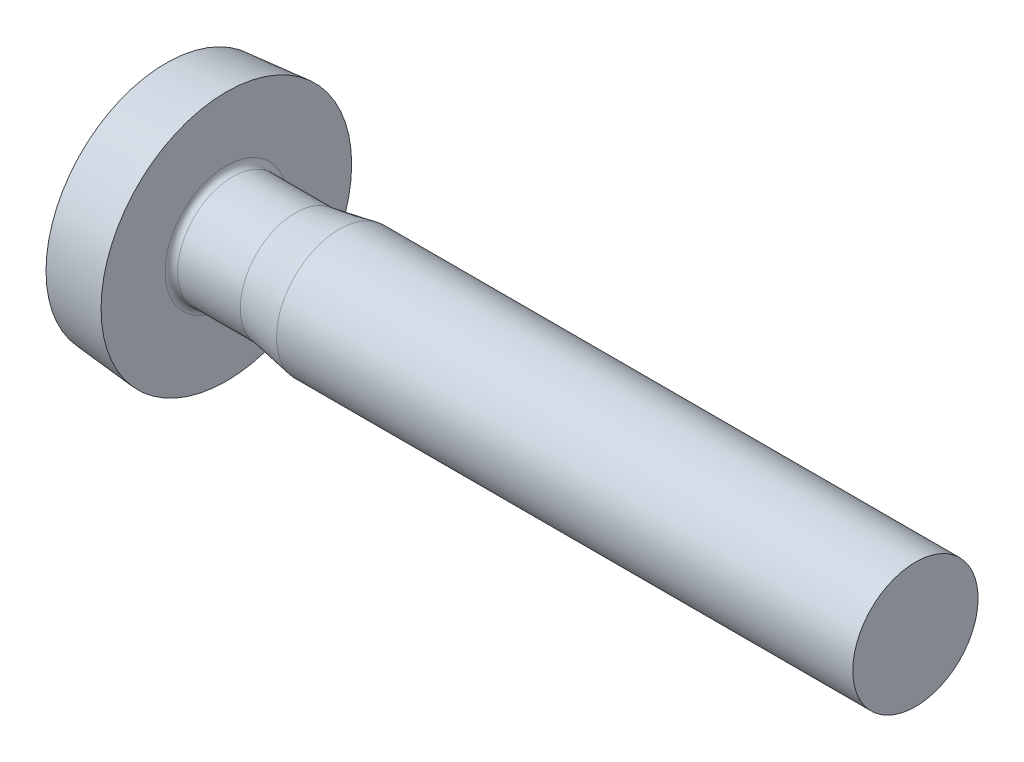
SolidWorks part; units mm, degrees
ref_plane "Front Plane" through (0, 0, 0) normal (0, 0, 1) x (1, 0, 0)
ref_plane "Top Plane" through (0, 0, 0) normal (0, 1, 0) x (1, 0, 0)
ref_plane "Right Plane" through (0, 0, 0) normal (1, 0, 0) x (0, 0, -1)
sketch "Sketch1" plane through (0, 0, 0) normal (0, 0, 1) x (1, 0, 0)
  line L0 (-0.9632, 1.9157) -> (0, 2)
  line L1 (0, 2) -> (0, 0.8772)
  line L2 (0, 0.8772) -> (1.1, 0.8772)
  line L3 (1.1, 0.8772) -> (1.8, 1)
  line L4 (1.8, 1) -> (11, 1)
  line L5 (11, 1) -> (11, 0)
  line L6 (11, 0) -> (-1.6, 0)
  line L7 (11, 0) -> (-1.6, 0) construction
  arc A0 (-1.6, 0) -> (-0.9632, 1.9157) centre (1.6, 0) cw
revolve "Revolve1" add sketch "Sketch1" angle 360 about L7 reverse direction yes
cosmetic thread "Cosmetic Thread1" parameters "D1"=9.2, "D2"=1.509
sketch "Sketch2" plane through (0, 0, 0) normal (0, 0, 1) x (1, 0, 0)
  line L0 (-0.1, 0.7773) -> (1.1, 0.7773)
  line L1 (1.1, 0.7773) -> (1.1, 0.8772)
  line L2 (1.1, 0.8772) -> (0.1, 0.8772)
  line L3 (0, 0.9773) -> (-0.1, 0.9773)
  line L4 (-0.1, 0.9773) -> (-0.1, 0.7773)
  line L5 (1.1, 0) -> (-0.1, 0) construction
  arc A0 (0.1, 0.8772) -> (0, 0.9773) centre (0.1, 0.9773) cw
revolve "Revolve2" add sketch "Sketch2" angle 360 about L5 reverse direction yes
ref_plane "Plane1" through (-1.6, 0, 0) normal (1, 0, 0) x (0, 0, -1)
sketch "Sketch3" plane through (-1.6, 0, 0) normal (1, 0, 0) x (0, 0, -1)
  line L0 (-0.95, 0.2375) -> (-0.95, -0.2375)
  line L1 (-0.95, -0.2375) -> (-0.38, -0.1876)
  line L2 (-0.38, -0.1876) -> (-0.2375, -0.2375)
  line L3 (-0.2375, -0.2375) -> (-0.1876, -0.38)
  line L4 (-0.1876, -0.38) -> (-0.2375, -0.95)
  line L5 (-0.2375, -0.95) -> (0.2375, -0.95)
  line L6 (0.2375, -0.95) -> (0.1876, -0.38)
  line L7 (0.1876, -0.38) -> (0.2375, -0.2375)
  line L8 (0.2375, -0.2375) -> (0.38, -0.1876)
  line L9 (0.38, -0.1876) -> (0.95, -0.2375)
  line L10 (0.95, -0.2375) -> (0.95, 0.2375)
  line L11 (0.95, 0.2375) -> (0.38, 0.1876)
  line L12 (0.38, 0.1876) -> (0.2375, 0.2375)
  line L13 (0.2375, 0.2375) -> (0.1876, 0.38)
  line L14 (0.1876, 0.38) -> (0.2375, 0.95)
  line L15 (0.2375, 0.95) -> (-0.2375, 0.95)
  line L16 (-0.2375, 0.95) -> (-0.1876, 0.38)
  line L17 (-0.1876, 0.38) -> (-0.2375, 0.2375)
  line L18 (-0.2375, 0.2375) -> (-0.38, 0.1876)
  line L19 (-0.38, 0.1876) -> (-0.95, 0.2375)
extrude "Cut-Extrude1" cut sketch "Sketch3" along normal blind 0.8
ref_plane "Plane2" through (11, 0, 0) normal (1, 0, 0) x (0, 0, -1)
ref_plane "Plane3" through (0, 0, 0) normal (0, 0, 1) x (1, 0, 0)
ref_plane "IP1 XY" through (0, 0, 0) normal (1, 0, 0) x (0, 0, -1)
ref_plane "IP1 XZ" through (0, 0, 0) normal (0, -1, 0) x (-1, 0, 0)
ref_plane "IP1 YZ" through (0, 0, 0) normal (0, 0, -1) x (-1, 0, 0)
ref_axis "IP1 X" through (0, 0, 80.9) along (0, 0, -1)
ref_axis "IP1 Y" through (0, -50, 0) along (0, 1, 0)
ref_axis "IP1 Z" through (80.9, 0, 0) along (-1, 0, 0)
sketch3d "IP1"
  point P0 (0, 0, 0)
ref_plane "IP3 XY" through (11, 0, 0) normal (1, 0, 0) x (0, 0, -1)
ref_plane "IP3 XZ" through (0, 0, 0) normal (0, -1, 0) x (-1, 0, 0)
ref_plane "IP3 YZ" through (0, 0, 0) normal (0, 0, -1) x (-1, 0, 0)
ref_axis "IP3 X" through (11, 0, 80.9) along (0, 0, -1)
ref_axis "IP3 Y" through (11, -50, 0) along (0, 1, 0)
ref_axis "IP3 Z" through (80.9, 0, 0) along (-1, 0, 0)
sketch3d "IP3"
  point P0 (11, 0, 0)
